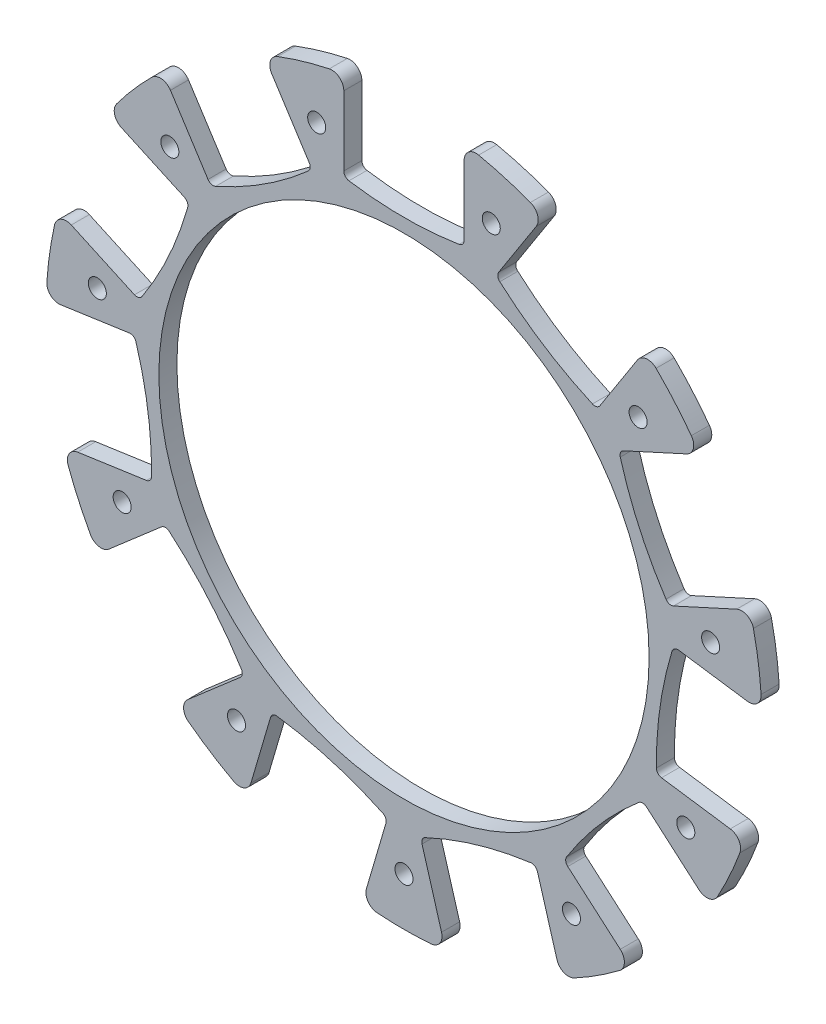
SolidWorks part; units mm, degrees
material "Thornel Mat VMA"
ref_plane "前视基准面" through (0, 0, 0) normal (0, 0, 1) x (1, 0, 0)
ref_plane "上视基准面" through (0, 0, 0) normal (0, 1, 0) x (1, 0, 0)
ref_plane "右视基准面" through (0, 0, 0) normal (1, 0, 0) x (0, 0, -1)
sketch "草图2" plane through (0, 0, 0) normal (0, 0, 1) x (1, 0, 0)
  line L0 (12.85, 52.4) -> (12.85, 55.6) construction
  line L1 (12.85, 55.6) -> (10, 55.6) construction
  line L2 (10, 52.4) -> (12.85, 52.4) construction
  line L3 (9.35, 50.9) -> (10, 50.9) construction
  line L4 (10, 50.9) -> (10, 57.1) construction
  line L5 (10, 57.1) -> (9.35, 57.1) construction
  line L6 (9.35, 46.1078) -> (9.35, 61.8922) construction
  line L7 (8.4948, 45.1184) -> (8.4948, 62.8816) construction
  line L8 (-8.4948, 62.8816) -> (-8.4948, 45.1184) construction
  line L9 (-9.35, 61.8922) -> (-9.35, 46.1078) construction
  line L10 (-10, 50.9) -> (-9.35, 50.9) construction
  line L11 (-9.35, 57.1) -> (-10, 57.1) construction
  line L12 (-10, 57.1) -> (-10, 50.9) construction
  line L13 (-10, 55.6) -> (-12.85, 55.6) construction
  line L14 (-12.85, 52.4) -> (-10, 52.4) construction
  line L15 (-12.85, 55.6) -> (-12.85, 52.4) construction
  line L16 (-8.4948, 54) -> (8.4948, 54) construction
  line L17 (10, 58.6536) -> (10, 43.8392)
  line L18 (-10, 58.6536) -> (-10, 43.8392)
  line L19 (40.1231, 43.9362) -> (32.1138, 31.4735)
  line L20 (23.298, 54.749) -> (15.2887, 42.2863)
  line L21 (57.5074, 15.2693) -> (44.0317, 9.1151)
  line L22 (49.1991, 33.4619) -> (35.7234, 27.3078)
  line L23 (56.6335, -18.2455) -> (41.9698, -16.1372)
  line L24 (59.4798, 1.5509) -> (44.8161, 3.6592)
  line L25 (37.7789, -45.9675) -> (26.5829, -36.2661)
  line L26 (50.8761, -30.8525) -> (39.6801, -21.1511)
  line L27 (6.9297, -59.0951) -> (2.756, -44.8807)
  line L28 (26.1196, -53.4604) -> (21.9459, -39.2461)
  line L29 (-26.1196, -53.4604) -> (-21.9459, -39.2461)
  line L30 (-6.9297, -59.0951) -> (-2.756, -44.8807)
  line L31 (-50.8761, -30.8525) -> (-39.6801, -21.1511)
  line L32 (-37.7789, -45.9675) -> (-26.5829, -36.2661)
  line L33 (-59.4798, 1.5509) -> (-44.8161, 3.6592)
  line L34 (-56.6335, -18.2455) -> (-41.9698, -16.1372)
  line L35 (-49.1991, 33.4619) -> (-35.7234, 27.3078)
  line L36 (-57.5074, 15.2693) -> (-44.0317, 9.1151)
  line L37 (-23.298, 54.749) -> (-15.2887, 42.2863)
  line L38 (-40.1231, 43.9362) -> (-32.1138, 31.4735)
  line L39 (0, 44.5) -> (0, 43) construction
  arc A0 (9.35, 61.8922) -> (8.4948, 62.8816) centre (8.35, 61.8922) ccw construction
  arc A1 (8.4948, 45.1184) -> (9.35, 46.1078) centre (8.35, 46.1078) ccw construction
  arc A2 (-8.4948, 45.1184) -> (8.4948, 45.1184) centre (0, 103.1567) ccw construction
  arc A3 (8.4948, 62.8816) -> (-8.4948, 62.8816) centre (0, 4.8433) ccw construction
  arc A4 (-8.4948, 62.8816) -> (-9.35, 61.8922) centre (-8.35, 61.8922) ccw construction
  arc A5 (-9.35, 46.1078) -> (-8.4948, 45.1184) centre (-8.35, 46.1078) ccw construction
  circle A6 centre (0, 0) radius 59.5 construction
  arc A7 (-10, 43.8392) -> (10, 43.8392) centre (0, 103) ccw
  arc A8 (15.2887, 42.2863) -> (32.1138, 31.4735) centre (55.686, 86.6491) ccw
  arc A9 (35.7234, 27.3078) -> (44.0317, 9.1151) centre (93.6921, 42.7877) ccw
  arc A10 (44.8161, 3.6592) -> (41.9698, -16.1372) centre (101.9516, -14.6584) ccw
  arc A11 (39.6801, -21.1511) -> (26.5829, -36.2661) centre (77.8422, -67.4507) ccw
  arc A12 (21.9459, -39.2461) -> (2.756, -44.8807) centre (29.0185, -98.8278) ccw
  arc A13 (-2.756, -44.8807) -> (-21.9459, -39.2461) centre (-29.0185, -98.8278) ccw
  arc A14 (-26.5829, -36.2661) -> (-39.6801, -21.1511) centre (-77.8422, -67.4507) ccw
  arc A15 (-41.9698, -16.1372) -> (-44.8161, 3.6592) centre (-101.9516, -14.6584) ccw
  arc A16 (-44.0317, 9.1151) -> (-35.7234, 27.3078) centre (-93.6921, 42.7877) ccw
  arc A17 (-32.1138, 31.4735) -> (-15.2887, 42.2863) centre (-55.686, 86.6491) ccw
  arc A18 (-23.298, 54.749) -> (-10, 58.6536) centre (0, 0) cw
  arc A19 (10, 58.6536) -> (23.298, 54.749) centre (0, 0) cw
  arc A20 (40.1231, 43.9362) -> (49.1991, 33.4619) centre (0, 0) cw
  arc A21 (57.5074, 15.2693) -> (59.4798, 1.5509) centre (0, 0) cw
  arc A22 (56.6335, -18.2455) -> (50.8761, -30.8525) centre (0, 0) cw
  arc A23 (37.7789, -45.9675) -> (26.1196, -53.4604) centre (0, 0) cw
  arc A24 (6.9297, -59.0951) -> (-6.9297, -59.0951) centre (0, 0) cw
  arc A25 (-49.1991, 33.4619) -> (-40.1231, 43.9362) centre (0, 0) cw
  arc A26 (-57.5074, 15.2693) -> (-59.4798, 1.5509) centre (0, 0) ccw
  arc A27 (-56.6335, -18.2455) -> (-50.8761, -30.8525) centre (0, 0) ccw
  arc A28 (-37.7789, -45.9675) -> (-26.1196, -53.4604) centre (0, 0) ccw
  circle A29 centre (0, 0) radius 63.5 construction
  circle A30 centre (0, 0) radius 40.75
  circle A31 centre (0, -51.5) radius 1.5
  circle A32 centre (-27.843, -43.3246) radius 1.5
  circle A33 centre (-46.846, -21.3939) radius 1.5
  circle A34 centre (-50.9758, 7.3292) radius 1.5
  circle A35 centre (-38.9211, 33.7253) radius 1.5
  circle A36 centre (-14.5092, 49.4139) radius 1.5
  circle A37 centre (14.5092, 49.4139) radius 1.5
  circle A38 centre (38.9211, 33.7253) radius 1.5
  circle A39 centre (50.9758, 7.3292) radius 1.5
  circle A40 centre (46.846, -21.3939) radius 1.5
  circle A41 centre (27.843, -43.3246) radius 1.5
  point P37 (-12.85, 54)
  point P41 (-9.675, 57.1)
  point P42 (-9.675, 50.9)
  point P43 (0, 63.5)
  point P44 (0, 44.5)
  point P45 (-10, 54)
  point P46 (-9.35, 54)
  point P47 (9.35, 54)
  point P48 (10, 54)
  point P49 (12.85, 54)
  point P54 (0, 54)
  point P108 (0, 0)
  point P132 (0, 0)
  dimension "D1" = 25.7
  dimension "D8" = 1
  dimension "D9" = 58.6567
  dimension "D11" = 119
  dimension "D12" = 60
  dimension "D15" = 127
  dimension "D16" = 81.5
  dimension "D17" = 3
  dimension "D2" = 3.2
  dimension "D3" = 6.2
  dimension "D4" = 20
  dimension "D5" = 19
  dimension "D6" = 18.7
  dimension "D7" = 54
  dimension "D10" = 16.9896
  dimension "D13" = 1.5
  dimension "D18" = 51.5
  dimension "D14" = 11
  dimension "D19" = 11
extrude "凸台-拉伸1" add sketch "草图2" along normal blind 3
fillet "圆角1" radius 1 22 edges at (10, 43.8392, 1.5) (-10, 43.8392, 1.5) (-15.2887, 42.2863, 1.5) (-32.1138, 31.4735, 1.5) (-35.7234, 27.3078, 1.5) (-44.0317, 9.1151, 1.5) (-44.8161, 3.6592, 1.5) (-41.9698, -16.1372, 1.5) (-39.6801, -21.1511, 1.5) (-26.5829, -36.2661, 1.5) (-21.9459, -39.2461, 1.5) (-2.756, -44.8807, 1.5) (2.756, -44.8807, 1.5) (21.9459, -39.2461, 1.5) (26.5829, -36.2661, 1.5) (39.6801, -21.1511, 1.5) (41.9698, -16.1372, 1.5) (44.8161, 3.6592, 1.5) (44.0317, 9.1151, 1.5) (35.7234, 27.3078, 1.5) (32.1138, 31.4735, 1.5) (15.2887, 42.2863, 1.5)
fillet "圆角2" radius 2 22 edges at (10, 58.6536, 1.5) (-10, 58.6536, 1.5) (-23.298, 54.749, 1.5) (-40.1231, 43.9362, 1.5) (-49.1991, 33.4619, 1.5) (-57.5074, 15.2693, 1.5) (-59.4798, 1.5509, 1.5) (-56.6335, -18.2455, 1.5) (-50.8761, -30.8525, 1.5) (-37.7789, -45.9675, 1.5) (-26.1196, -53.4604, 1.5) (-6.9297, -59.0951, 1.5) (6.9297, -59.0951, 1.5) (26.1196, -53.4604, 1.5) (37.7789, -45.9675, 1.5) (50.8761, -30.8525, 1.5) (56.6335, -18.2455, 1.5) (59.4798, 1.5509, 1.5) (57.5074, 15.2693, 1.5) (49.1991, 33.4619, 1.5) (40.1231, 43.9362, 1.5) (23.298, 54.749, 1.5)
ref_axis "基准轴1" through (0, 0, 3) along (0, 0, -1)
